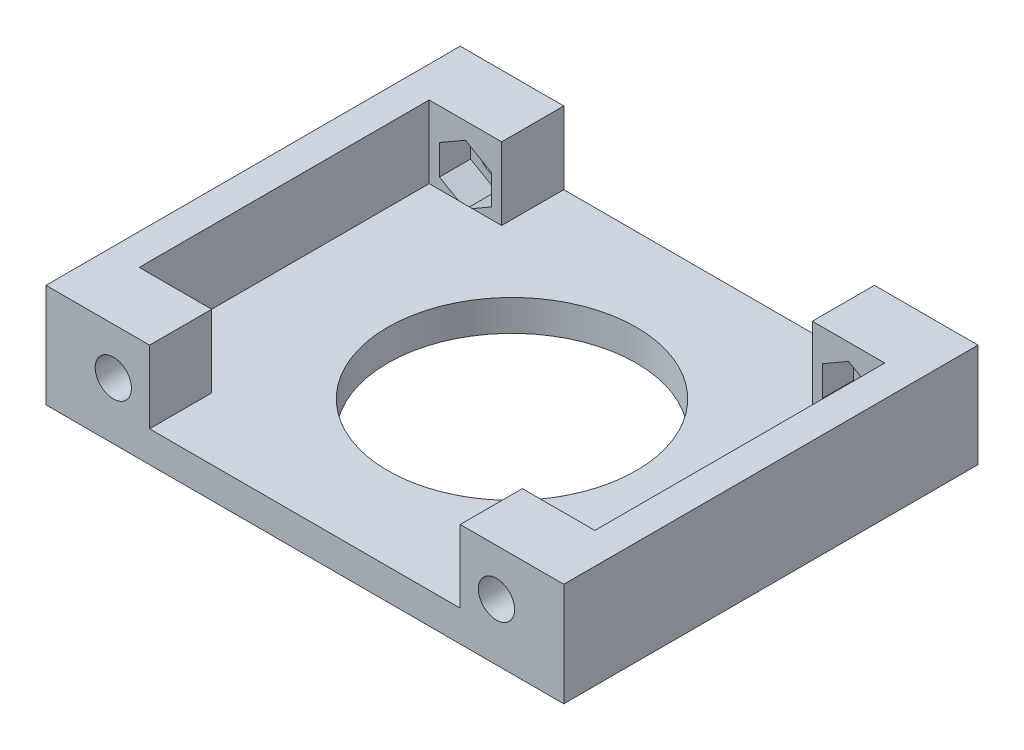
SolidWorks part; units mm, degrees
ref_plane "Front Plane" through (0, 0, 0) normal (0, 0, 1) x (1, 0, 0)
ref_plane "Top Plane" through (0, 0, 0) normal (0, 1, 0) x (1, 0, 0)
ref_plane "Right Plane" through (0, 0, 0) normal (1, 0, 0) x (0, 0, -1)
sketch "Sketch1" plane through (0, 0, 0) normal (0, 1, 0) x (1, 0, 0)
  line L1 (-25, 20) -> (25, 20)
  line L2 (-25, 20) -> (-25, -20)
  line L3 (-25, -20) -> (25, -20)
  line L4 (25, 20) -> (25, -20)
  line L5 (-25, 20) -> (25, -20) construction
  line L6 (-25, -20) -> (25, 20) construction
  point P0 (0, 0)
  dimension "D1" = 50
  dimension "D2" = 40
extrude "Boss-Extrude1" add sketch "Sketch1" along normal blind 3
sketch "Sketch2" plane through (0, 3, 0) normal (0, 1, 0) x (1, 0, 0)
  circle A0 centre (0, 0) radius 12
  dimension "D1" = 24
extrude "Cut-Extrude1" cut sketch "Sketch2" against normal through all
sketch "Sketch3" plane through (0, 3, 0) normal (0, 1, 0) x (1, 0, 0)
  line L0 (-25, -20) -> (25, -20) construction
  line L1 (-25, 20) -> (-22, 20)
  line L2 (-25, 20) -> (-25, -20)
  line L3 (-25, -20) -> (-22, -20)
  line L4 (-22, 20) -> (-22, -20)
  line L6 (22, -20) -> (25, -20)
  line L7 (22, -20) -> (22, 20)
  line L8 (22, 20) -> (25, 20)
  line L9 (25, -20) -> (25, 20)
  dimension "D1" = 3
extrude "Boss-Extrude2" add sketch "Sketch3" along normal blind 7
sketch "Sketch4" plane through (0, 0, 20) normal (0, 0, 1) x (1, 0, 0)
  line L1 (-22, 3) -> (-15, 3)
  line L2 (-22, 3) -> (-22, 10)
  line L3 (-22, 10) -> (-15, 10)
  line L4 (-15, 3) -> (-15, 10)
  line L5 (22, 3) -> (15, 3)
  line L6 (22, 3) -> (22, 10)
  line L7 (22, 10) -> (15, 10)
  line L8 (15, 3) -> (15, 10)
  dimension "D2" = 7
  dimension "6" = 7
extrude "Boss-Extrude3" add sketch "Sketch4" against normal blind 6
sketch "Sketch5" plane through (0, 0, 20) normal (0, 0, 1) x (1, 0, 0)
  line L0 (-18.5, 10) -> (-18.5, 5.5) construction
  line L2 (18.5, 10) -> (18.5, 5.5) construction
  line L3 (-25, 0) -> (25, 0) construction
  line L4 (-18.5, 5.5) -> (18.5, 5.5) construction
  line L6 (-22, 10) -> (-15, 10) construction
  line L7 (-25, 10) -> (-15, 10) construction
  line L8 (15, 10) -> (22, 10) construction
  line L9 (15, 10) -> (15, 3) construction
  line L10 (15, 10) -> (25, 10) construction
  circle A0 centre (-18.5, 5.5) radius 1.75
  circle A1 centre (18.5, 5.5) radius 1.75
  dimension "D1" = 3.5
  dimension "D2" = 3.5
  dimension "D3" = 5.5
extrude "Cut-Extrude2" cut sketch "Sketch5" against normal through all
mirror "Mirror1" about plane through (0, 0, 0) normal (0, 0, 1) of "Cut-Extrude2", "Boss-Extrude3"
sketch "Sketch6" plane through (0, 0, -14) normal (0, 0, 1) x (1, 0, 0)
  line L1 (-18.5, 2.6132) -> (-16, 4.0566)
  line L2 (-16, 4.0566) -> (-16, 6.9434)
  line L3 (-16, 6.9434) -> (-18.5, 8.3868)
  line L4 (-18.5, 8.3868) -> (-21, 6.9434)
  line L5 (-21, 6.9434) -> (-21, 4.0566)
  line L6 (-21, 4.0566) -> (-18.5, 2.6132)
  circle A0 centre (-18.5, 5.5) radius 2.5 construction
  dimension "D1" = 5
extrude "Cut-Extrude3" cut sketch "Sketch6" against normal blind 3
mirror "Mirror2" about plane through (0, 0, 0) normal (1, 0, 0) of "Cut-Extrude3"
mirror "Mirror3" about plane through (0, 0, 0) normal (0, 0, 1) of "Mirror2"
